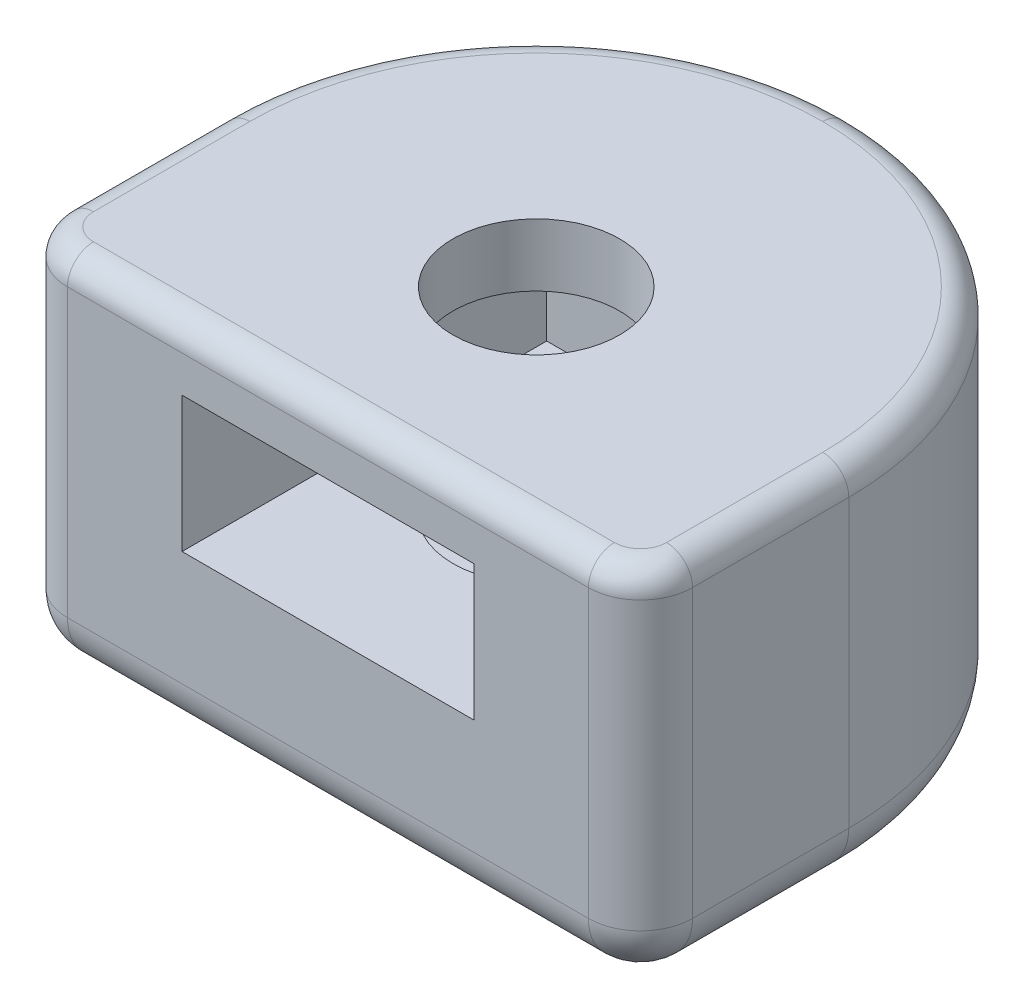
SolidWorks part; units mm, degrees
ref_plane "Front Plane" through (0, 0, 0) normal (0, 0, 1) x (1, 0, 0)
ref_plane "Top Plane" through (0, 0, 0) normal (0, 1, 0) x (1, 0, 0)
ref_plane "Right Plane" through (0, 0, 0) normal (1, 0, 0) x (0, 0, -1)
sketch "Sketch1" plane through (0, 0, 0) normal (0, 1, 0) x (1, 0, 0)
  line L1 (0, 0) -> (12, 0)
  line L2 (0, 0) -> (0, 10)
  line L3 (0, 10) -> (12, 10)
  line L4 (12, 0) -> (12, 10)
  dimension "D1" = 12
  dimension "D2" = 10
extrude "Boss-Extrude1" add sketch "Sketch1" along normal blind 7
sketch "Sketch2" plane through (0, 7, 0) normal (0, 1, 0) x (1, 0, 0)
  line L0 (0, 0) -> (12, 0) construction
  line L1 (12, 0) -> (12, 10) construction
  circle A0 centre (6, 4) radius 1.6
  dimension "D1" = 3.2
  dimension "D2" = 4
  dimension "D3" = 6
extrude "Cut-Extrude1" cut sketch "Sketch2" against normal blind 4
sketch "Sketch3" plane through (0, 0, 0) normal (0, 0, 1) x (1, 0, 0)
  line L0 (0, 7) -> (12, 7) construction
  line L1 (3.2, 5.8) -> (8.8, 5.8)
  line L2 (3.2, 5.8) -> (3.2, 3.2)
  line L3 (3.2, 3.2) -> (8.8, 3.2)
  line L4 (8.8, 5.8) -> (8.8, 3.2)
  point P6 (6, 5.8)
  point P7 (6, 7)
  dimension "D1" = 5.6
  dimension "D2" = 2.6
  dimension "D3" = 1.2
extrude "Cut-Extrude2" cut sketch "Sketch3" against normal blind 7
fillet "Fillet1" radius 6 2 edges at (0, 3.5, -10) (12, 3.5, -10)
fillet "Fillet2" radius 1 4 edges at (0, 0, -2) (12, 0, -2) (10.2426, 0, -8.2426) (1.7574, 0, -8.2426)
fillet "Fillet3" radius 1 5 edges at (0, 4, 0) (0.2929, 0.2929, 0) (12, 4, 0) (11.7071, 0.2929, 0) (6, 0, 0)
fillet "Fillet4" radius 0.5 7 edges at (0.2929, 7, -0.2929) (0, 7, -2.5) (1.7574, 7, -8.2426) (10.2426, 7, -8.2426) (12, 7, -2.5) (11.7071, 7, -0.2929) (6, 7, 0)
